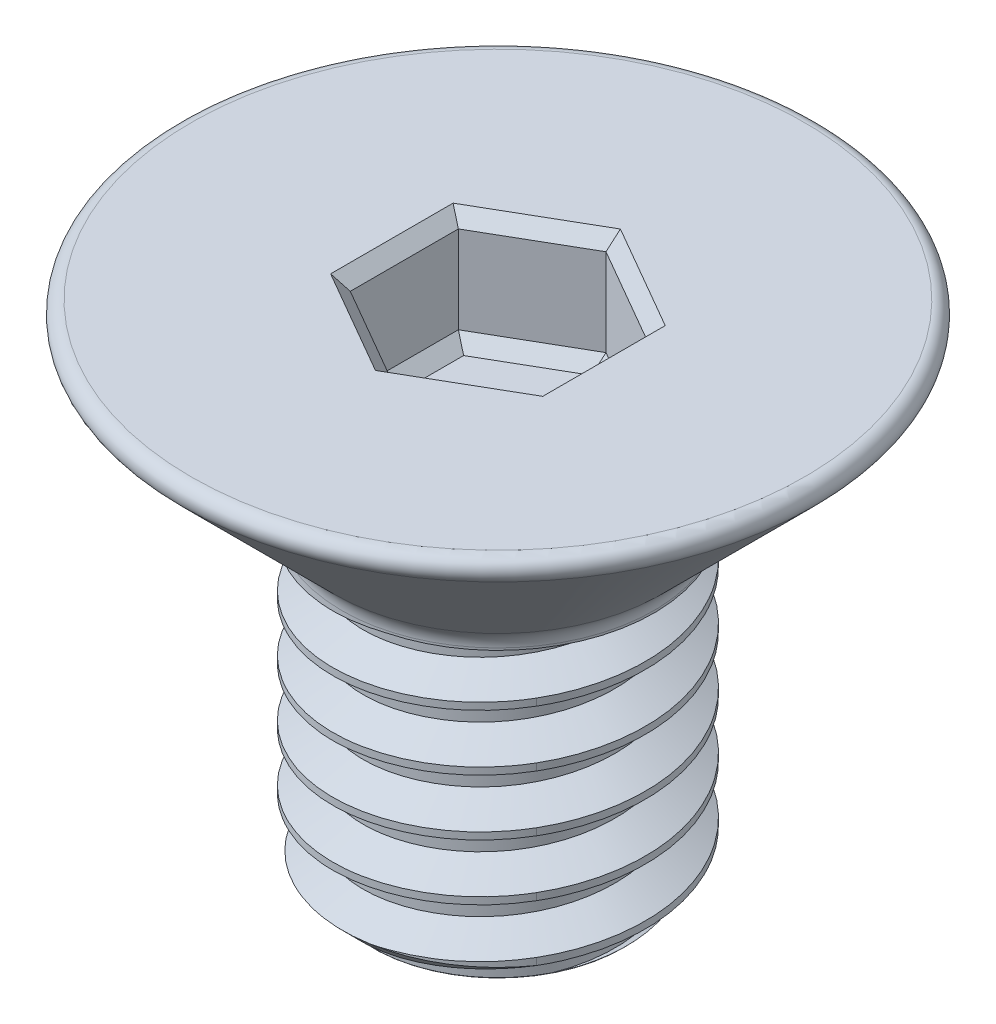
SolidWorks part; units mm, degrees
material "AISI Type A2 Tool Steel"
ref_plane "Front Plane" through (0, 0, 0) normal (0, 0, 1) x (1, 0, 0)
ref_plane "Top Plane" through (0, 0, 0) normal (0, 1, 0) x (1, 0, 0)
ref_plane "Right Plane" through (0, 0, 0) normal (1, 0, 0) x (0, 0, -1)
sketch "Sketch1" plane through (0, 0, 0) normal (0, 1, 0) x (1, 0, 0)
  circle A0 centre (0, 0) radius 1.25
  dimension "D1" = 2.5
extrude "Boss-Extrude1" add sketch "Sketch1" along normal blind 2.45
thread "Thread1" pitch 0.45 method cut profile "Thread Profile1" start angle 0, offset 1, length 0, pitch 0.45, diameter 2.5
ref_plane "Plane1" through (1.25, -1, 0) normal (0, 0, 1) x (1, 0, 0)
sketch "Thread Profile1" plane through (1.25, -1, 0) normal (0, 0, 1) x (1, 0, 0)
  line L0 (0, 0) -> (0, 0.45) construction
  line L11 (0, 0) -> (0, 0.3937)
  line L12 (0, 0.3937) -> (-0.2436, 0.2531)
  line L13 (-0.2436, 0.2531) -> (-0.2436, 0.1406)
  line L15 (-0.2436, 0.1406) -> (0, 0)
  line L17 (-0.2436, 0.1969) -> (0, 0.1969) construction
  point P2 (0, 0)
  dimension "Pitch" = 0.45
  dimension "Profile_Angle" = 60
  dimension "Profile_Land" = 0.1125
  dimension "Profile_Height" = 0.2436
sketch "Sketch5" plane through (0, 2.45, 0) normal (0, 1, 0) x (1, 0, 0)
  circle A0 centre (0, 0) radius 1.25
  dimension "D1" = 2.5
extrude "Boss-Extrude2" add sketch "Sketch5" along normal blind 0.1
sketch "Sketch6" plane through (0, 2.55, 0) normal (0, 1, 0) x (1, 0, 0)
  circle A0 centre (0, 0) radius 1.25
  dimension "D1" = 2.5
extrude "Boss-Extrude3" add sketch "Sketch6" along normal blind 1.45 draft 45 draft outward yes
fillet "Fillet1" radius 0.2 1 edges at (0, 2.55, 1.25)
fillet "Fillet2" radius 0.1 1 edges at (0, 4, 2.7)
sketch "Sketch7" plane through (0, 0, 0) normal (0, 0, 1) x (1, 0, 0)
  line L0 (0, 0) -> (0, 0.3237) construction
  line L1 (0, 0) -> (1.26, 0) construction
  line L2 (1.26, 0) -> (1.26, 0.26)
  line L3 (1.26, 0.26) -> (1, 0)
  line L4 (1, 0) -> (1.26, 0)
  dimension "D1" = 45
  dimension "D2" = 0.26
  dimension "D3" = 1.26
revolve "Cut-Revolve1" cut sketch "Sketch7" angle 360 about L0
sketch "Sketch8" plane through (0, 4, 0) normal (0, 1, 0) x (1, 0, 0)
  line L1 (0, 0.866) -> (-0.75, 0.433)
  line L2 (-0.75, 0.433) -> (-0.75, -0.433)
  line L3 (-0.75, -0.433) -> (0, -0.866)
  line L4 (0, -0.866) -> (0.75, -0.433)
  line L5 (0.75, -0.433) -> (0.75, 0.433)
  line L6 (0.75, 0.433) -> (0, 0.866)
  circle A0 centre (0, 0) radius 0.75 construction
  dimension "D1" = 1.5
extrude "Cut-Extrude1" cut sketch "Sketch8" against normal blind 0.8
chamfer "Chamfer1" distance 0.1 angle 45 6 edges at (-0.75, 4, 0) (-0.375, 4, 0.6495) (0.375, 4, 0.6495) (0.75, 4, 0) (0.375, 4, -0.6495) (-0.375, 4, -0.6495)
sketch "Sketch9" plane through (0, 3.2, 0) normal (0, 1, 0) x (1, 0, 0)
  line L1 (0, 0.866) -> (-0.75, 0.433)
  line L2 (-0.75, 0.433) -> (-0.75, -0.433)
  line L3 (-0.75, -0.433) -> (0, -0.866)
  line L4 (0, -0.866) -> (0.75, -0.433)
  line L5 (0.75, -0.433) -> (0.75, 0.433)
  line L6 (0.75, 0.433) -> (0, 0.866)
  circle A0 centre (0, 0) radius 0.75 construction
extrude "Cut-Extrude2" cut sketch "Sketch9" against normal blind 0.1 draft 45
